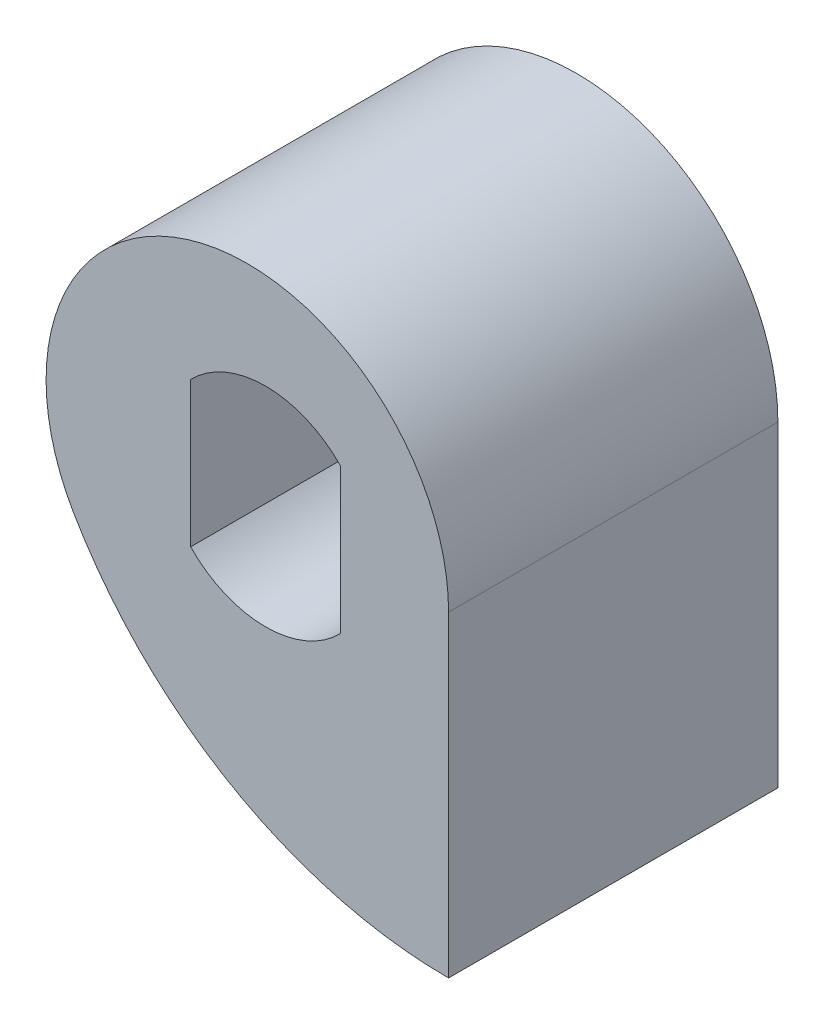
SolidWorks part; units mm, degrees
ref_plane "Спереди" through (0, 0, 0) normal (0, 0, 1) x (1, 0, 0)
ref_plane "Сверху" through (0, 0, 0) normal (0, 1, 0) x (1, 0, 0)
ref_plane "Справа" through (0, 0, 0) normal (1, 0, 0) x (0, 0, -1)
sketch "Эскиз1" plane through (0, 0, 0) normal (0, 0, 1) x (1, 0, 0)
  line L0 (-2.05, 1.9799) -> (-2.05, -1.9799)
  line L1 (2.05, 1.9799) -> (2.05, -1.9799)
  line L2 (5, 0) -> (5, -8.6603)
  arc A1 (-2.05, -1.9799) -> (2.05, -1.9799) centre (0, 0) ccw
  arc A2 (2.05, 1.9799) -> (-2.05, 1.9799) centre (0, 0) ccw
  circle A11 centre (0, 0) radius 5 construction
  arc A28 (5, -8.6603) -> (-5.2517, -2.7697) centre (5, 3.2059) cw
  arc A31 (-5.2517, -2.7697) -> (5, 0) centre (-0.5, 0) cw
  point P1 (-5.2941, -4.6191)
  point P9 (-6.5195, -1.9799)
  point P10 (-6.5195, -2.1122)
  point P12 (-6.8718, -0.1323)
  dimension "D1" = 5.7
  dimension "D3" = 10
  dimension "D5" = 5.5
  dimension "D2" = 4.1
  dimension "D4" = 5
extrude "Улитка с пазом под буёк сбоку" add sketch "Эскиз1" along normal blind 4.5 and the other way blind 4.5
sketch "Эскиз2" [suppressed] plane through (0, 0, 0) normal (0, 0, 1) x (1, 0, 0)
  line L0 (-2.05, 1.9799) -> (-2.05, -1.9799)
  line L1 (2.05, 1.9799) -> (2.05, -1.9799)
  line L3 (0, -6) -> (0, -11)
  arc A0 (-2.05, -1.9799) -> (2.05, -1.9799) centre (0, 0) ccw
  arc A1 (2.05, 1.9799) -> (-2.05, 1.9799) centre (0, 0) ccw
  arc A3 (0, -6) -> (0, 6) centre (0, 0) ccw
  arc A5 (0, 6) -> (0, -11) centre (0, -2.5) ccw
  dimension "D1" = 5.7
  dimension "D4" = 11
  dimension "D2" = 4.1
  dimension "D3" = 5
extrude "Улитка с пазом под буёк по центру" [suppressed] add sketch "Эскиз2" along normal blind 9
